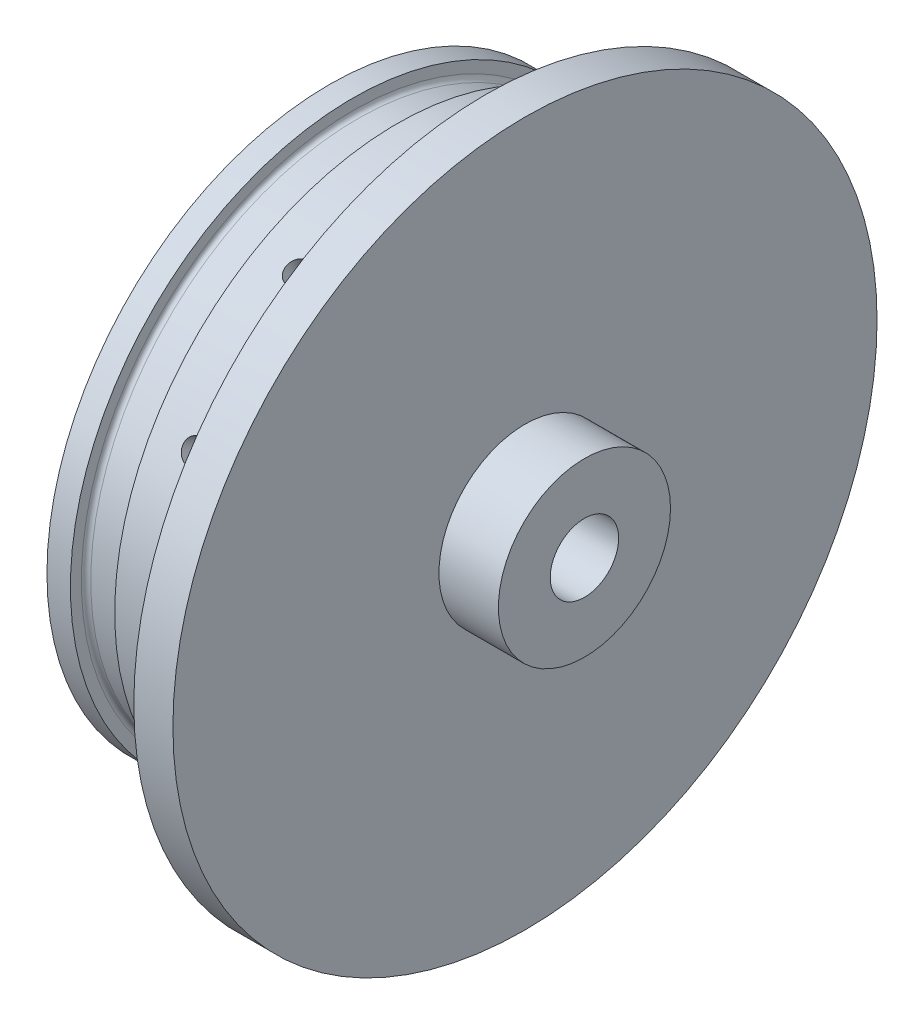
SolidWorks part; units mm, degrees
material "7075-T6 (SN)"
ref_plane "Front Plane" through (0, 0, 0) normal (0, 0, 1) x (1, 0, 0)
ref_plane "Top Plane" through (0, 0, 0) normal (0, 1, 0) x (1, 0, 0)
ref_plane "Right Plane" through (0, 0, 0) normal (1, 0, 0) x (0, 0, -1)
sketch "Sketch1" plane through (0, 0, 0) normal (1, 0, 0) x (0, 0, -1)
  circle A0 centre (0, 0) radius 57.15
  dimension "D1" = 114.3
extrude "Boss-Extrude1" add sketch "Sketch1" along normal blind 6.35
sketch "Sketch2" plane through (0, 0, 0) normal (-1, 0, 0) x (0, 0, 1)
  circle A0 centre (0, 0) radius 45.847
  dimension "D1" = 91.694
extrude "Boss-Extrude2" add sketch "Sketch2" along normal blind 25.4
sketch "Sketch10" plane through (0, 0, 0) normal (0, 1, 0) x (1, 0, 0)
  line L0 (0, 0) -> (-53.2238, 0) construction
  line L1 (-26.2636, 0) -> (26.2636, 0) construction
  line L2 (0, 0) -> (0, 64.5447) construction
  line L3 (0, -62.865) -> (0, 62.865) construction
ref_plane "Plane1" through (0, 0, -45.847) normal (0, 0, -1) x (-1, 0, 0)
sketch "Sketch11" plane through (0, 0, -45.847) normal (0, 0, -1) x (-1, 0, 0)
  line L0 (0, 0) -> (53.2238, 0) construction
  line L1 (0, -45.847) -> (0, 45.847) construction
  circle A0 centre (7.62, 0) radius 1.8986
  dimension "D2" = 3.7973
  dimension "D1" = 7.62
extrude "Cut-Extrude3" cut sketch "Sketch11" against normal blind 10.16
pattern_circular "CirPattern1" count 12 over 360 about axis through (0, 0, 0) along (-1, 0, 0) of "Cut-Extrude3" reverse direction yes
sketch "Sketch15" plane through (6.35, 0, 0) normal (1, 0, 0) x (0, 0, -1)
  circle A0 centre (0, 0) radius 5.5562
  dimension "D1" = 11.1125
extrude "Cut-Extrude4" cut sketch "Sketch15" against normal through all both and the other way through all
sketch "Sketch16" plane through (0, 0, 0) normal (0, 0, 1) x (1, 0, 0)
  line L0 (-9.5186, 45.847) -> (-25.4, 45.847) construction
  line L1 (-21.59, 45.847) -> (-14.4018, 45.847)
  line L2 (-21.59, 45.847) -> (-21.59, 44.069)
  line L3 (-20.828, 43.307) -> (-15.1638, 43.307)
  line L4 (-14.4018, 45.847) -> (-14.4018, 44.069)
  line L5 (0, 0) -> (-53.2238, 0) construction
  line L6 (-25.4, 45.847) -> (-25.4, -45.847) construction
  arc A0 (-14.4018, 44.069) -> (-15.1638, 43.307) centre (-15.1638, 44.069) cw
  arc A1 (-20.828, 43.307) -> (-21.59, 44.069) centre (-20.828, 44.069) cw
  point P8 (-26.6119, 0)
  point P13 (-14.4018, 43.307)
  point P16 (-21.59, 43.307)
  dimension "D4" = 0.762
  dimension "D1" = 43.307
  dimension "D2" = 3.81
  dimension "D3" = 7.1882
revolve "Cut-Revolve1" cut sketch "Sketch16" angle 360 about L0
sketch "Sketch17" plane through (6.35, 0, 0) normal (1, 0, 0) x (0, 0, -1)
  circle A0 centre (0, 0) radius 13.97
  circle A1 centre (0, 0) radius 5.5562
  dimension "D1" = 27.94
  dimension "D2" = 11.1125
extrude "Boss-Extrude3" add sketch "Sketch17" along normal blind 9.652
cosmetic thread "Cosmetic Thread1" parameters "D2"=23.1953
sketch "Sketch18" plane through (-25.4, 0, 0) normal (-1, 0, 0) x (0, 0, 1)
  circle A0 centre (0, 0) radius 38.354
  dimension "D1" = 76.708
extrude "Cut-Extrude5" cut sketch "Sketch18" against normal blind 6.604
sketch "Sketch19" plane through (-18.796, 0, 0) normal (-1, 0, 0) x (0, 0, 1)
  line L0 (0, 0) -> (0, 57.15) construction
  circle A0 centre (0, 0) radius 57.15 construction
  circle A1 centre (0, 33.3375) radius 1.1303
  circle A2 centre (23.5732, 23.5732) radius 1.1303
  circle A3 centre (33.3375, 0) radius 1.1303
  circle A4 centre (23.5732, -23.5732) radius 1.1303
  circle A5 centre (0, -33.3375) radius 1.1303
  circle A6 centre (-23.5732, -23.5732) radius 1.1303
  circle A7 centre (-33.3375, 0) radius 1.1303
  circle A8 centre (-23.5732, 23.5732) radius 1.1303
  point P24 (0, 0)
  dimension "D2" = 2.2606
  dimension "D1" = 33.3375
  dimension "D3" = 8
extrude "Cut-Extrude6" cut sketch "Sketch19" against normal blind 6.35
sketch "Sketch20" plane through (0, 0, 0) normal (0, 0, 1) x (1, 0, 0)
  line L0 (0, 0) -> (-18.796, 0)
  line L1 (-18.796, 27.94) -> (0, 15.875)
  line L3 (-18.796, 27.94) -> (-18.796, 0)
  line L4 (0, 45.847) -> (0, -45.847) construction
  line L5 (0, 15.875) -> (0, 0)
  dimension "D1" = 27.94
  dimension "D2" = 18.796
  dimension "D3" = 15.875
revolve "Cut-Revolve2" cut sketch "Sketch20" angle 360 about L0
